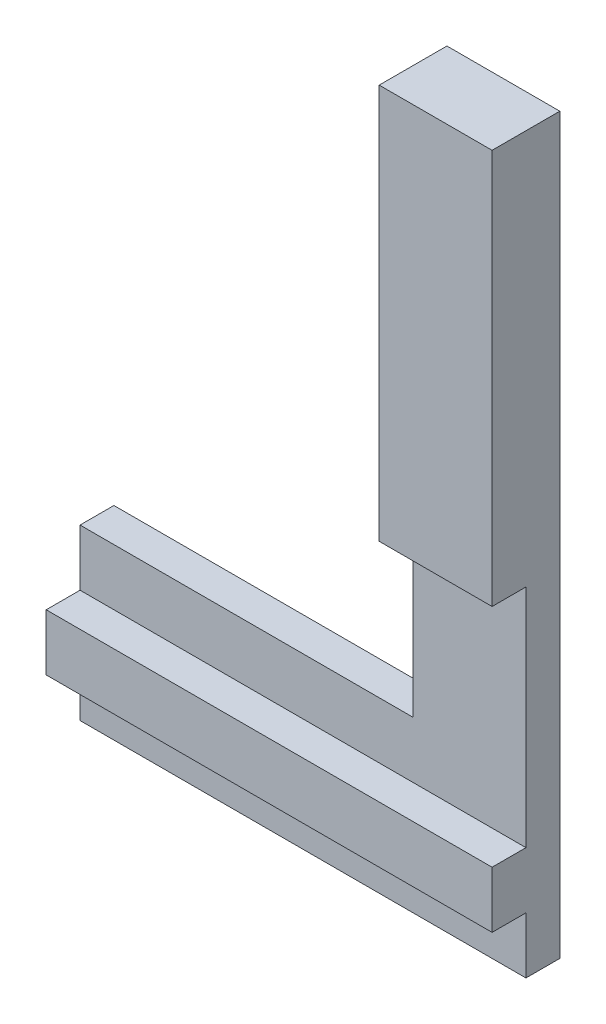
SolidWorks part; units mm, degrees
ref_plane "Front Plane" through (0, 0, 0) normal (0, 0, 1) x (1, 0, 0)
ref_plane "Top Plane" through (0, 0, 0) normal (0, 1, 0) x (1, 0, 0)
ref_plane "Right Plane" through (0, 0, 0) normal (1, 0, 0) x (0, 0, -1)
sketch "Sketch1" plane through (0, 0, 0) normal (0, 0, 1) x (1, 0, 0)
  line L3 (79, 0) -> (0, 0)
  line L4 (0, 0) -> (0, -30)
  line L5 (0, -30) -> (79, -30)
  line L6 (79, -30) -> (79, 0)
  line L9 (0, 0) -> (20, 0)
  line L26 (0, 0) -> (0, -30)
  line L28 (79, 0) -> (59, 0)
  line L29 (79, 0) -> (79, 100)
  line L30 (79, 100) -> (59, 100)
  line L31 (59, 0) -> (59, 100)
  dimension "D1" = 20
  dimension "D2" = 100
  dimension "D3" = 79
  dimension "D4" = 30
extrude "Boss-Extrude4" add sketch "Sketch1" along normal blind 6 contours L31 L3 region at (69, 50, 0)
extrude "Boss-Extrude5" add sketch "Sketch1<8>" along normal blind 6 contours L5 L6 L3 L4 region at (39.5, -15, 0)
sketch "Sketch1<8>" plane through (0, 0, 0) normal (0, 0, 1) x (1, 0, 0) same geometry as "Sketch1"
sketch "Sketch3" plane through (0, 0, 6) normal (0, 0, 1) x (1, 0, 0)
  line L1 (0, -10) -> (79, -10)
  line L2 (0, -10) -> (0, -20)
  line L3 (0, -20) -> (79, -20)
  line L4 (79, -10) -> (79, -20)
  line L5 (79, -30) -> (79, 100) construction
  dimension "D1" = 10
  dimension "D2" = 10
extrude "Boss-Extrude6" add sketch "Sketch3" along normal blind 6
sketch "Sketch6" plane through (0, 0, 6) normal (0, 0, 1) x (1, 0, 0)
  line L5 (79, -10) -> (79, 100) construction
  line L6 (59, 100) -> (79, 100)
  line L7 (59, 100) -> (59, 30)
  line L8 (59, 30) -> (79, 30)
  line L9 (79, 100) -> (79, 30)
  line M5 (59, 100) -> (59, 0)
  dimension "D1" = 70
extrude "Boss-Extrude8" add sketch "Sketch6" along normal blind 6 contours M5 region at (69, 65, 6)
